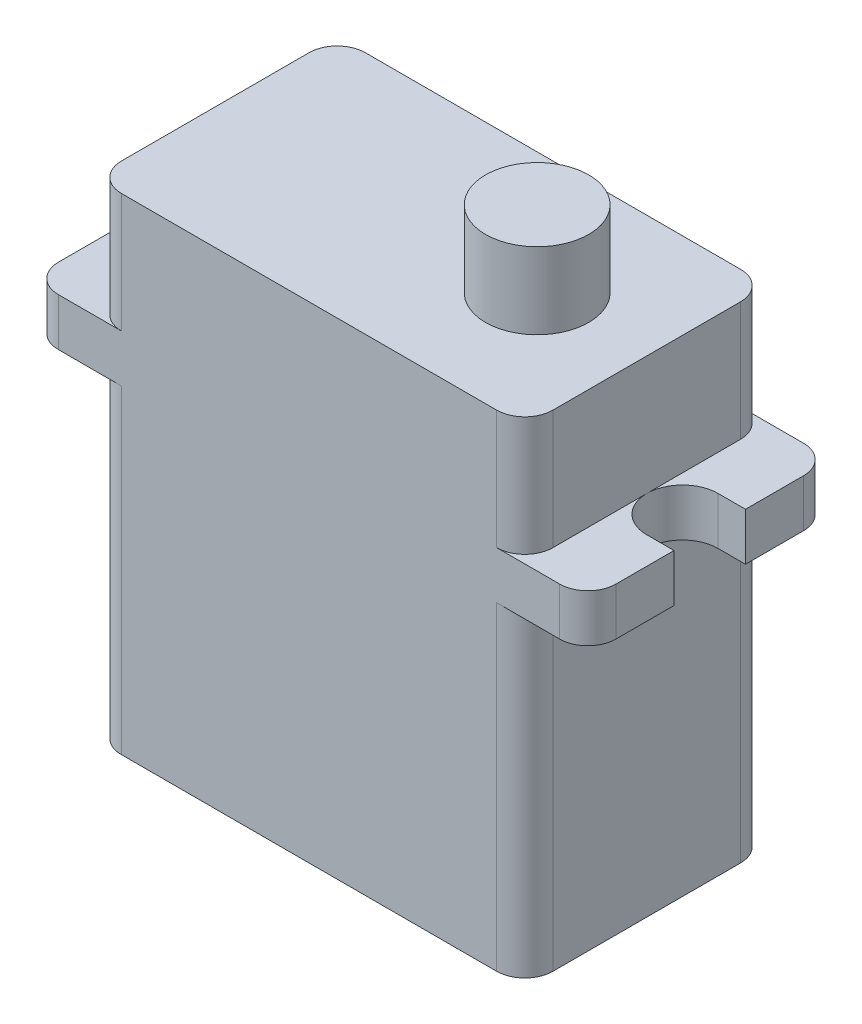
SolidWorks part; units mm, degrees
ref_plane "Front Plane" through (0, 0, 0) normal (0, 0, 1) x (1, 0, 0)
ref_plane "Top Plane" through (0, 0, 0) normal (0, 1, 0) x (1, 0, 0)
ref_plane "Right Plane" through (0, 0, 0) normal (1, 0, 0) x (0, 0, -1)
sketch "Sketch2" plane through (0, 0, 0) normal (0, 1, 0) x (1, 0, 0)
  line L1 (1.5, 0) -> (21.5, 0)
  line L2 (0, -1.5) -> (0, -11.5)
  line L3 (1.5, -13) -> (21.5, -13)
  line L4 (23, -1.5) -> (23, -11.5)
  arc A0 (21.5, -13) -> (23, -11.5) centre (21.5, -11.5) ccw
  arc A1 (1.5, -13) -> (0, -11.5) centre (1.5, -11.5) cw
  arc A2 (0, -1.5) -> (1.5, 0) centre (1.5, -1.5) cw
  arc A3 (23, -1.5) -> (21.5, 0) centre (21.5, -1.5) ccw
  point P7 (23, -13)
  point P12 (0, 0)
  point P15 (23, 0)
  dimension "D3" = 1.5
  dimension "D1" = 23
  dimension "D2" = 13
extrude "Boss-Extrude1" add sketch "Sketch2" along normal blind 17.018 contours L2 A1 L3 A0 L4 A3 L1 A2
sketch "Sketch3" plane through (0, 17.018, 0) normal (0, 1, 0) x (1, 0, 0)
  line L0 (1.5, -13) -> (21.5, -13) construction
  line L1 (-1.859, 0) -> (24.859, 0)
  line L2 (-3.359, -1.5) -> (-3.359, -11.5)
  line L3 (-1.859, -13) -> (24.859, -13)
  line L4 (26.359, -1.5) -> (26.359, -11.5)
  line L5 (1.5, 0) -> (21.5, 0) construction
  line L6 (23, -1.5) -> (23, -11.5) construction
  line L7 (24.905, -4.595) -> (26.359, -4.595)
  line L11 (1.5, 0) -> (21.5, 0) construction
  line L12 (24.905, -8.405) -> (26.359, -8.405)
  line L13 (0, -1.5) -> (0, -11.5) construction
  line L14 (-1.905, -4.595) -> (-3.359, -4.595)
  line L15 (-1.905, -8.405) -> (-3.359, -8.405)
  circle A1 centre (-1.905, -6.5) radius 1.905
  circle A3 centre (24.905, -6.5) radius 1.905
  arc A4 (24.859, -13) -> (26.359, -11.5) centre (24.859, -11.5) ccw
  arc A5 (26.359, -1.5) -> (24.859, 0) centre (24.859, -1.5) ccw
  arc A6 (-1.859, -13) -> (-3.359, -11.5) centre (-1.859, -11.5) cw
  arc A7 (-3.359, -1.5) -> (-1.859, 0) centre (-1.859, -1.5) cw
  point P13 (26.359, -6.5)
  point P21 (11.5, 0)
  point P28 (26.359, 0)
  point P33 (-3.359, 0)
  point P34 (11.5, 0)
  point P35 (11.5, -13)
  arc M13 (1.5, 0) -> (0, -1.5) centre (1.5, -1.5) ccw
  line M14 (0, -1.5) -> (0, -11.5)
  arc M15 (0, -11.5) -> (1.5, -13) centre (1.5, -11.5) ccw
  line M16 (1.5, -13) -> (21.5, -13)
  arc M17 (21.5, -13) -> (23, -11.5) centre (21.5, -11.5) ccw
  line M18 (23, -11.5) -> (23, -1.5)
  arc M19 (23, -1.5) -> (21.5, 0) centre (21.5, -1.5) ccw
  line M20 (21.5, 0) -> (1.5, 0)
  dimension "D3" = 1.5
  dimension "D2" = 3.81
  dimension "D1" = 29.718
extrude "Boss-Extrude2" add sketch "Sketch3" along normal blind 2.54 contours M20 M13 M14 M15 M16 M17 M18 M19 | A6 L3 A1 L15 L2 M15 M14 | A7 L2 L14 A1 L1 M14 M13 | L3 A4 L4 L12 A3 M18 M17 | L4 A5 L1 A3 L7 M19 M18 region at (-1.5192, 17.018, 2.4283) region at (11.5, 17.018, 6.5) region at (24.5192, 17.018, 2.4283) region at (-1.5192, 17.018, 10.5717) region at (24.5192, 17.018, 10.5717)
sketch "Sketch4" plane through (0, 19.558, 0) normal (0, 1, 0) x (1, 0, 0)
  line L0 (1.5, 0) -> (21.5, 0)
  line L1 (23, -1.5) -> (23, -11.5)
  line L2 (21.5, -13) -> (1.5, -13)
  line L4 (0, -11.5) -> (0, -1.5)
  arc A0 (21.5, -13) -> (23, -11.5) centre (21.5, -11.5) ccw
  arc A1 (21.5, 0) -> (23, -1.5) centre (21.5, -1.5) cw
  arc A2 (0, -11.5) -> (1.5, -13) centre (1.5, -11.5) ccw
  arc A3 (0, -1.5) -> (1.5, 0) centre (1.5, -1.5) cw
  circle A4 centre (17.158, -6.5) radius 2.75
  point P12 (23, -13)
  point P15 (23, 0)
  point P18 (0, -13)
  point P21 (0, 0)
  dimension "D1" = 1.5
  dimension "D2" = 5.5
  dimension "D3" = 5.842
extrude "Boss-Extrude3" add sketch "Sketch4" along normal blind 6.35 contours L4 A3 L0 A1 L1 A0 L2 A2
extrude "Boss-Extrude4" add sketch "Sketch4<4>" along normal blind 10.414 contours A4 region at (17.158, 19.558, 6.5)
sketch "Sketch4<4>" plane through (0, 19.558, 0) normal (0, 1, 0) x (1, 0, 0) same geometry as "Sketch4"
